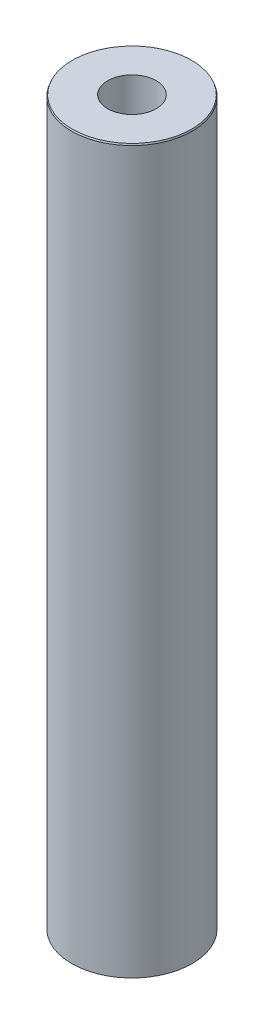
SolidWorks part; units mm, degrees
ref_plane "Front Plane" through (0, 0, 0) normal (0, 0, 1) x (1, 0, 0)
ref_plane "Top Plane" through (0, 0, 0) normal (0, 1, 0) x (1, 0, 0)
ref_plane "Right Plane" through (0, 0, 0) normal (1, 0, 0) x (0, 0, -1)
sketch "Sketch1" plane through (0, 0, 0) normal (0, 1, 0) x (1, 0, 0)
  circle A0 centre (0, 0) radius 50
  dimension "SHAFT_OD" = 100
extrude "Boss-Extrude1" add sketch "Sketch1" along normal blind 600
sketch "Sketch2" plane through (0, 0, 0) normal (0, 1, 0) x (1, 0, 0)
  circle A0 centre (0, 0) radius 20.1542
  dimension "BORE_D" = 40.3085
extrude "Cut-Extrude1" cut sketch "Sketch2" along normal through all
chamfer "Chamfer1" distance 1.2436 angle 21.346 2 edges at (0, 600, 50) (0, 0, 50) first distance on face at (0, 600, 50) first distance on face at (0, 0, 20.1542)
